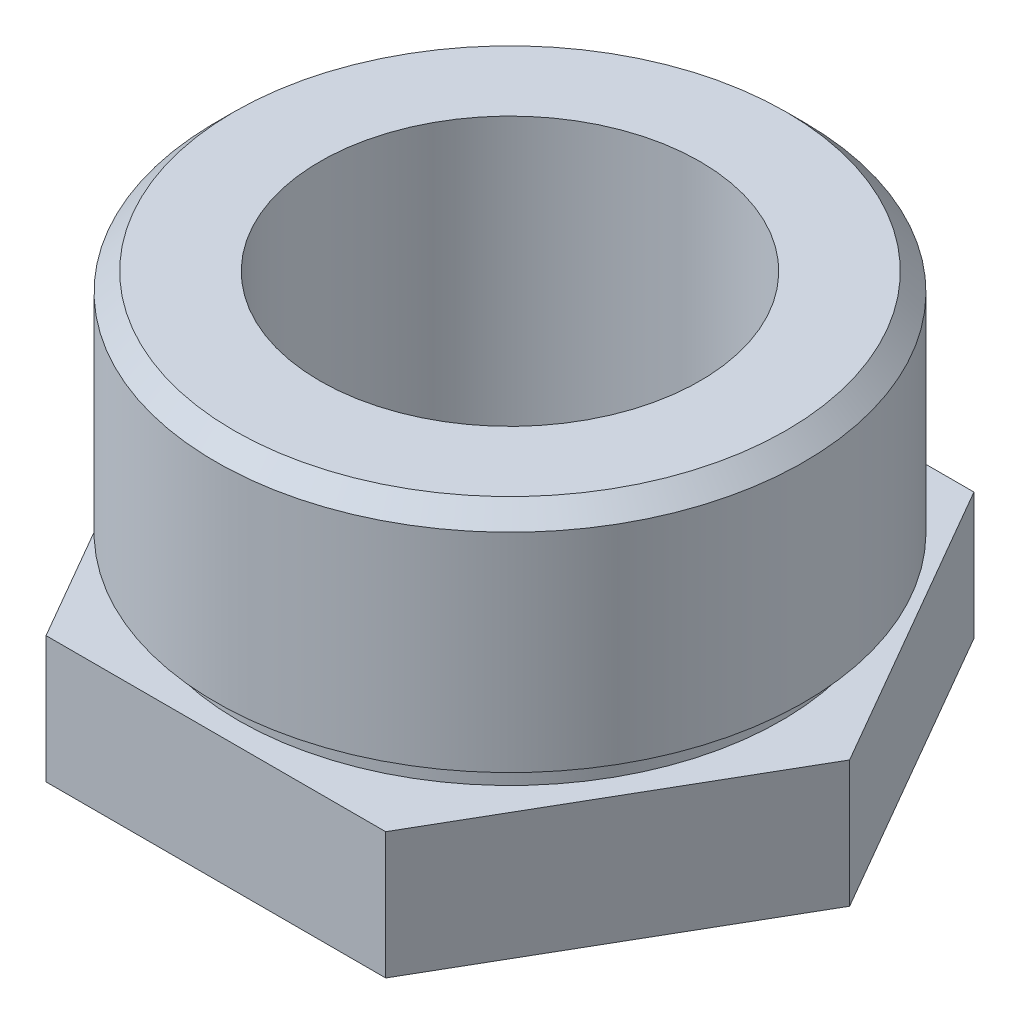
SolidWorks part; units mm, degrees
ref_plane "Front Plane" through (0, 0, 0) normal (0, 0, 1) x (1, 0, 0)
ref_plane "Top Plane" through (0, 0, 0) normal (0, 1, 0) x (1, 0, 0)
ref_plane "Right Plane" through (0, 0, 0) normal (1, 0, 0) x (0, 0, -1)
sketch "Sketch1" plane through (0, 0, 0) normal (0, 1, 0) x (1, 0, 0)
  line L1 (37.5278, 0) -> (18.7639, 32.5)
  line L2 (18.7639, 32.5) -> (-18.7639, 32.5)
  line L3 (-18.7639, 32.5) -> (-37.5278, 0)
  line L4 (-37.5278, 0) -> (-18.7639, -32.5)
  line L5 (-18.7639, -32.5) -> (18.7639, -32.5)
  line L6 (18.7639, -32.5) -> (37.5278, 0)
  circle A0 centre (0, 0) radius 32.5
  circle A1 centre (0, 0) radius 21
  circle A2 centre (0, 0) radius 30
  dimension "D1" = 42
  dimension "D2" = 65
  dimension "D3" = 60
extrude "Boss-Extrude1" add sketch "Sketch1" along normal blind 14 contours L5 L6 L1 L2 L3 L4 A2 | A2 A1 | A0 L1 L2 | A0 L2 L3 | A0 L6 L1 | A0 L5 L6 | A0 L4 L5 | A0 L3 L4 region at (33.5908, 0, 0) region at (16.7954, 0, -29.0905) region at (30.5047, 0, -8.1737) region at (16.7954, 0, 29.0905) region at (-16.7954, 0, -29.0905) region at (-16.7954, 0, 29.0905) region at (-33.5908, 0, 0) region at (-29.1515, 0, 0)
extrude "Boss-Extrude2" add sketch "Sketch1<3>" along normal blind 42 contours A2 A1 | A0 A2 region at (30.5047, 0, -8.1737) region at (-29.1515, 0, 0)
sketch "Sketch1<3>" plane through (0, 0, 0) normal (0, 1, 0) x (1, 0, 0) same geometry as "Sketch1"
extrude "Cut-Extrude1" cut sketch "Sketch1<4>" along normal blind 3 from surface contours A0 A2 region at (30.5047, 0, -8.1737) starting at face at (-16.3623, 14, -28.3403)
sketch "Sketch1<4>" plane through (0, 0, 0) normal (0, 1, 0) x (1, 0, 0) same geometry as "Sketch1"
chamfer "Chamfer2" distance 2 angle 45 1 edges at (0, 42, 32.5)
cosmetic thread "Cosmetic Thread1" parameters "D1"=22.9999, "D2"=64
